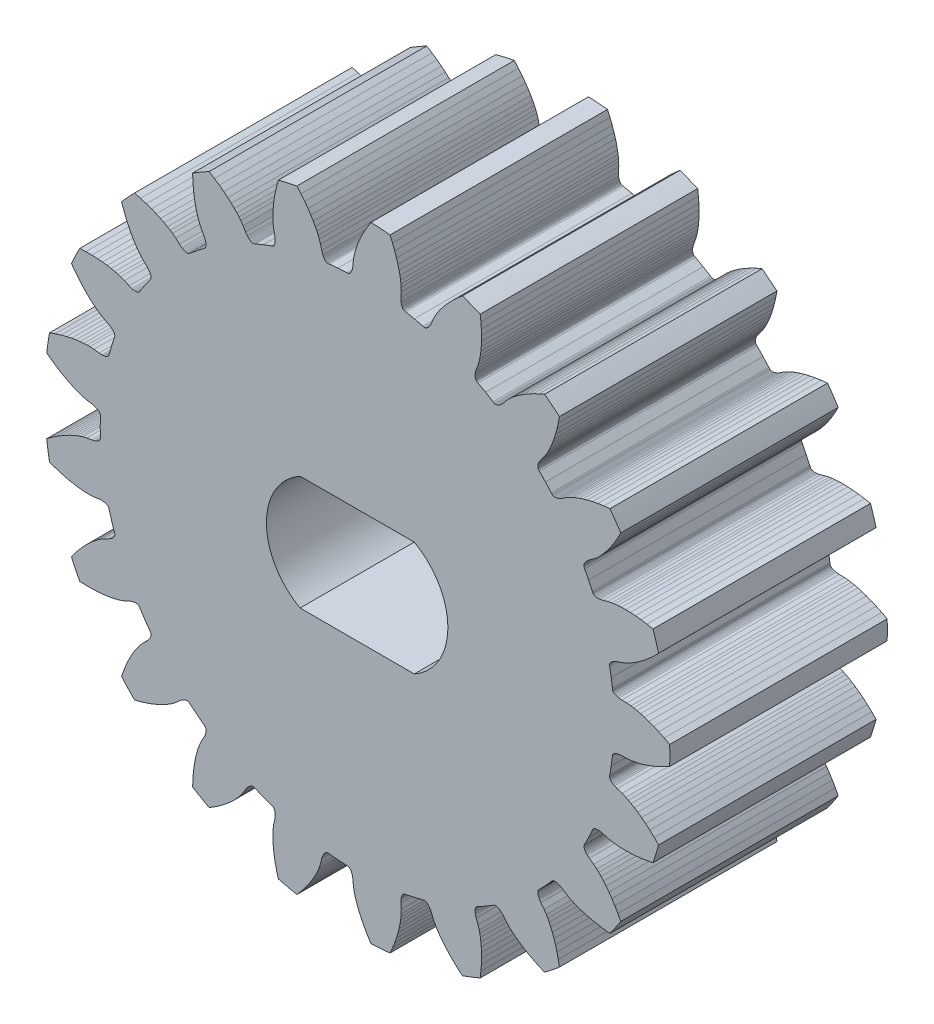
SolidWorks part; units mm, degrees
ref_plane "Front Plane" through (0, 0, 0) normal (0, 0, 1) x (1, 0, 0)
ref_plane "Top Plane" through (0, 0, 0) normal (0, 1, 0) x (1, 0, 0)
ref_plane "Right Plane" through (0, 0, 0) normal (1, 0, 0) x (0, 0, -1)
sketch "Model" plane through (0, 0, 0) normal (0, 0, 1) x (1, 0, 0)
  line L0 (10.9267, 2.8918) -> (10.7633, 2.7404)
  line L1 (10.7633, 2.7404) -> (10.6079, 2.6079)
  line L2 (10.6079, 2.6079) -> (10.4602, 2.4924)
  line L3 (10.4602, 2.4924) -> (10.3215, 2.3929)
  line L4 (10.3215, 2.3929) -> (10.1944, 2.3095)
  line L5 (10.1944, 2.3095) -> (10.0772, 2.2395)
  line L6 (10.0772, 2.2395) -> (9.9721, 2.1826)
  line L7 (9.9721, 2.1826) -> (9.8817, 2.1384)
  line L8 (9.8817, 2.1384) -> (9.7426, 2.0805)
  line L9 (9.7426, 2.0805) -> (9.5615, 2.023)
  line L10 (9.5615, 2.023) -> (9.4651, 1.9818)
  line L11 (9.4651, 1.9818) -> (9.4245, 1.9597)
  line L12 (9.4245, 1.9597) -> (9.3889, 1.9369)
  line L13 (9.3889, 1.9369) -> (9.3585, 1.9135)
  line L14 (9.3585, 1.9135) -> (9.3331, 1.8898)
  line L15 (9.3331, 1.8898) -> (9.3128, 1.866)
  line L16 (9.3128, 1.866) -> (9.2976, 1.8422)
  line L17 (9.2976, 1.8422) -> (9.2875, 1.8187)
  line L18 (9.2875, 1.8187) -> (9.2824, 1.7958)
  line L19 (9.2824, 1.7958) -> (9.2824, 1.7734)
  line L20 (9.2824, 1.7734) -> (9.291, 1.7262)
  line L21 (9.291, 1.7262) -> (9.3445, 1.4084)
  line L22 (9.3445, 1.4084) -> (9.3871, 1.0891)
  line L23 (9.3871, 1.0891) -> (9.3927, 1.0414)
  line L24 (9.3927, 1.0414) -> (9.3994, 1.0201)
  line L25 (9.3994, 1.0201) -> (9.411, 0.9996)
  line L26 (9.411, 0.9996) -> (9.4276, 0.9802)
  line L27 (9.4276, 0.9802) -> (9.4491, 0.9619)
  line L28 (9.4491, 0.9619) -> (9.4755, 0.9451)
  line L29 (9.4755, 0.9451) -> (9.5067, 0.93)
  line L30 (9.5067, 0.93) -> (9.5427, 0.9166)
  line L31 (9.5427, 0.9166) -> (9.5834, 0.9053)
  line L32 (9.5834, 0.9053) -> (9.6287, 0.8961)
  line L33 (9.6287, 0.8961) -> (9.733, 0.8852)
  line L34 (9.733, 0.8852) -> (9.923, 0.8836)
  line L35 (9.923, 0.8836) -> (10.073, 0.8693)
  line L36 (10.073, 0.8693) -> (10.1724, 0.8537)
  line L37 (10.1724, 0.8537) -> (10.2896, 0.8303)
  line L38 (10.2896, 0.8303) -> (10.4222, 0.7979)
  line L39 (10.4222, 0.7979) -> (10.5682, 0.7558)
  line L40 (10.5682, 0.7558) -> (10.7301, 0.7016)
  line L41 (10.7301, 0.7016) -> (10.9053, 0.6347)
  line L42 (10.9053, 0.6347) -> (11.0929, 0.5539)
  line L43 (11.0929, 0.5539) -> (11.2936, 0.4574)
  line L44 (11.2936, 0.4574) -> (11.4947, 0.3502)
  line L45 (11.4947, -0.3502) -> (11.2936, -0.4574)
  line L46 (11.2936, -0.4574) -> (11.0929, -0.5539)
  line L47 (11.0929, -0.5539) -> (10.9053, -0.6347)
  line L48 (10.9053, -0.6347) -> (10.7301, -0.7016)
  line L49 (10.7301, -0.7016) -> (10.5682, -0.7558)
  line L50 (10.5682, -0.7558) -> (10.4222, -0.7979)
  line L51 (10.4222, -0.7979) -> (10.2896, -0.8303)
  line L52 (10.2896, -0.8303) -> (10.1724, -0.8537)
  line L53 (10.1724, -0.8537) -> (10.073, -0.8693)
  line L54 (10.073, -0.8693) -> (9.923, -0.8836)
  line L55 (9.923, -0.8836) -> (9.733, -0.8852)
  line L56 (9.733, -0.8852) -> (9.6287, -0.8961)
  line L57 (9.6287, -0.8961) -> (9.5834, -0.9053)
  line L58 (9.5834, -0.9053) -> (9.5427, -0.9166)
  line L59 (9.5427, -0.9166) -> (9.5067, -0.93)
  line L60 (9.5067, -0.93) -> (9.4755, -0.9451)
  line L61 (9.4755, -0.9451) -> (9.4491, -0.9619)
  line L62 (9.4491, -0.9619) -> (9.4276, -0.9802)
  line L63 (9.4276, -0.9802) -> (9.411, -0.9996)
  line L64 (9.411, -0.9996) -> (9.3994, -1.0201)
  line L65 (9.3994, -1.0201) -> (9.3927, -1.0414)
  line L66 (9.3927, -1.0414) -> (9.3871, -1.0891)
  line L67 (9.3871, -1.0891) -> (9.3445, -1.4084)
  line L68 (9.3445, -1.4084) -> (9.291, -1.7262)
  line L69 (9.291, -1.7262) -> (9.2824, -1.7734)
  line L70 (9.2824, -1.7734) -> (9.2824, -1.7958)
  line L71 (9.2824, -1.7958) -> (9.2875, -1.8187)
  line L72 (9.2875, -1.8187) -> (9.2976, -1.8422)
  line L73 (9.2976, -1.8422) -> (9.3128, -1.866)
  line L74 (9.3128, -1.866) -> (9.3331, -1.8898)
  line L75 (9.3331, -1.8898) -> (9.3585, -1.9135)
  line L76 (9.3585, -1.9135) -> (9.3889, -1.9369)
  line L77 (9.3889, -1.9369) -> (9.4245, -1.9597)
  line L78 (9.4245, -1.9597) -> (9.4651, -1.9818)
  line L79 (9.4651, -1.9818) -> (9.5615, -2.023)
  line L80 (9.5615, -2.023) -> (9.7426, -2.0805)
  line L81 (9.7426, -2.0805) -> (9.8817, -2.1384)
  line L82 (9.8817, -2.1384) -> (9.9721, -2.1826)
  line L83 (9.9721, -2.1826) -> (10.0772, -2.2395)
  line L84 (10.0772, -2.2395) -> (10.1944, -2.3095)
  line L85 (10.1944, -2.3095) -> (10.3215, -2.3929)
  line L86 (10.3215, -2.3929) -> (10.4602, -2.4924)
  line L87 (10.4602, -2.4924) -> (10.6079, -2.6079)
  line L88 (10.6079, -2.6079) -> (10.7633, -2.7404)
  line L89 (10.7633, -2.7404) -> (10.9267, -2.8918)
  line L90 (10.9267, -2.8918) -> (11.0872, -3.0535)
  line L91 (10.8808, -3.7227) -> (10.657, -3.7659)
  line L92 (10.657, -3.7659) -> (10.4368, -3.799)
  line L93 (10.4368, -3.799) -> (10.2338, -3.8209)
  line L94 (10.2338, -3.8209) -> (10.0466, -3.8332)
  line L95 (10.0466, -3.8332) -> (9.8759, -3.8372)
  line L96 (9.8759, -3.8372) -> (9.724, -3.8345)
  line L97 (9.724, -3.8345) -> (9.5877, -3.8263)
  line L98 (9.5877, -3.8263) -> (9.4689, -3.8142)
  line L99 (9.4689, -3.8142) -> (9.3693, -3.7997)
  line L100 (9.3693, -3.7997) -> (9.2217, -3.7692)
  line L101 (9.2217, -3.7692) -> (9.0397, -3.7147)
  line L102 (9.0397, -3.7147) -> (8.9368, -3.6944)
  line L103 (8.9368, -3.6944) -> (8.8908, -3.6898)
  line L104 (8.8908, -3.6898) -> (8.8486, -3.6886)
  line L105 (8.8486, -3.6886) -> (8.8103, -3.6908)
  line L106 (8.8103, -3.6908) -> (8.7759, -3.6961)
  line L107 (8.7759, -3.6961) -> (8.7458, -3.7044)
  line L108 (8.7458, -3.7044) -> (8.7198, -3.7154)
  line L109 (8.7198, -3.7154) -> (8.6982, -3.7291)
  line L110 (8.6982, -3.7291) -> (8.6811, -3.7453)
  line L111 (8.6811, -3.7453) -> (8.6685, -3.7637)
  line L112 (8.6685, -3.7637) -> (8.649, -3.8076)
  line L113 (8.649, -3.8076) -> (8.5142, -4.1002)
  line L114 (8.5142, -4.1002) -> (8.3695, -4.3881)
  line L115 (8.3695, -4.3881) -> (8.3473, -4.4307)
  line L116 (8.3473, -4.4307) -> (8.3407, -4.452)
  line L117 (8.3407, -4.452) -> (8.3388, -4.4755)
  line L118 (8.3388, -4.4755) -> (8.3416, -4.5009)
  line L119 (8.3416, -4.5009) -> (8.3491, -4.5281)
  line L120 (8.3491, -4.5281) -> (8.3614, -4.5568)
  line L121 (8.3614, -4.5568) -> (8.3787, -4.587)
  line L122 (8.3787, -4.587) -> (8.4009, -4.6183)
  line L123 (8.4009, -4.6183) -> (8.4281, -4.6506)
  line L124 (8.4281, -4.6506) -> (8.4604, -4.6837)
  line L125 (8.4604, -4.6837) -> (8.5404, -4.7514)
  line L126 (8.5404, -4.7514) -> (8.6965, -4.8598)
  line L127 (8.6965, -4.8598) -> (8.8124, -4.9561)
  line L128 (8.8124, -4.9561) -> (8.8858, -5.025)
  line L129 (8.8858, -5.025) -> (8.9694, -5.1103)
  line L130 (8.9694, -5.1103) -> (9.0607, -5.2117)
  line L131 (9.0607, -5.2117) -> (9.1576, -5.3289)
  line L132 (9.1576, -5.3289) -> (9.2609, -5.4648)
  line L133 (9.2609, -5.4648) -> (9.3679, -5.6188)
  line L134 (9.3679, -5.6188) -> (9.4774, -5.7912)
  line L135 (9.4774, -5.7912) -> (9.5889, -5.984)
  line L136 (9.5889, -5.984) -> (9.6946, -6.1858)
  line L137 (9.3001, -6.7645) -> (9.0736, -6.7398)
  line L138 (9.0736, -6.7398) -> (8.8533, -6.7065)
  line L139 (8.8533, -6.7065) -> (8.6529, -6.6676)
  line L140 (8.6529, -6.6676) -> (8.4704, -6.6242)
  line L141 (8.4704, -6.6242) -> (8.3061, -6.5777)
  line L142 (8.3061, -6.5777) -> (8.1617, -6.5303)
  line L143 (8.1617, -6.5303) -> (8.0339, -6.4824)
  line L144 (8.0339, -6.4824) -> (7.9239, -6.4357)
  line L145 (7.9239, -6.4357) -> (7.833, -6.3926)
  line L146 (7.833, -6.3926) -> (7.701, -6.3199)
  line L147 (7.701, -6.3199) -> (7.5431, -6.2141)
  line L148 (7.5431, -6.2141) -> (7.4508, -6.1645)
  line L149 (7.4508, -6.1645) -> (7.4082, -6.1465)
  line L150 (7.4082, -6.1465) -> (7.3682, -6.1329)
  line L151 (7.3682, -6.1329) -> (7.331, -6.1237)
  line L152 (7.331, -6.1237) -> (7.2966, -6.1186)
  line L153 (7.2966, -6.1186) -> (7.2653, -6.1177)
  line L154 (7.2653, -6.1177) -> (7.2373, -6.1206)
  line L155 (7.2373, -6.1206) -> (7.2126, -6.1273)
  line L156 (7.2126, -6.1273) -> (7.1915, -6.1377)
  line L157 (7.1915, -6.1377) -> (7.174, -6.1515)
  line L158 (7.174, -6.1515) -> (7.1425, -6.1878)
  line L159 (7.1425, -6.1878) -> (6.9273, -6.4276)
  line L160 (6.9273, -6.4276) -> (6.7042, -6.6601)
  line L161 (6.7042, -6.6601) -> (6.6705, -6.6942)
  line L162 (6.6705, -6.6942) -> (6.6579, -6.7127)
  line L163 (6.6579, -6.7127) -> (6.6492, -6.7346)
  line L164 (6.6492, -6.7346) -> (6.6443, -6.7597)
  line L165 (6.6443, -6.7597) -> (6.6435, -6.7879)
  line L166 (6.6435, -6.7879) -> (6.6468, -6.819)
  line L167 (6.6468, -6.819) -> (6.6544, -6.8528)
  line L168 (6.6544, -6.8528) -> (6.6664, -6.8893)
  line L169 (6.6664, -6.8893) -> (6.6829, -6.9282)
  line L170 (6.6829, -6.9282) -> (6.704, -6.9693)
  line L171 (6.704, -6.9693) -> (6.7605, -7.0577)
  line L172 (6.7605, -7.0577) -> (6.8777, -7.2072)
  line L173 (6.8777, -7.2072) -> (6.9601, -7.3334)
  line L174 (6.9601, -7.3334) -> (7.0099, -7.4208)
  line L175 (7.0099, -7.4208) -> (7.0646, -7.527)
  line L176 (7.0646, -7.527) -> (7.122, -7.6509)
  line L177 (7.122, -7.6509) -> (7.1801, -7.7914)
  line L178 (7.1801, -7.7914) -> (7.2387, -7.9517)
  line L179 (7.2387, -7.9517) -> (7.2956, -8.1304)
  line L180 (7.2956, -8.1304) -> (7.3494, -8.3274)
  line L181 (7.3494, -8.3274) -> (7.399, -8.5445)
  line L182 (7.399, -8.5445) -> (7.4406, -8.7685)
  line L183 (6.893, -9.2052) -> (6.6839, -9.1149)
  line L184 (6.6839, -9.1149) -> (6.4832, -9.0181)
  line L185 (6.4832, -9.0181) -> (6.3032, -8.9218)
  line L186 (6.3032, -8.9218) -> (6.1416, -8.8266)
  line L187 (6.1416, -8.8266) -> (5.9983, -8.7338)
  line L188 (5.9983, -8.7338) -> (5.8743, -8.6459)
  line L189 (5.8743, -8.6459) -> (5.7663, -8.5624)
  line L190 (5.7663, -8.5624) -> (5.6749, -8.4854)
  line L191 (5.6749, -8.4854) -> (5.6008, -8.4174)
  line L192 (5.6008, -8.4174) -> (5.4961, -8.309)
  line L193 (5.4961, -8.309) -> (5.3764, -8.1614)
  line L194 (5.3764, -8.1614) -> (5.3028, -8.0868)
  line L195 (5.3028, -8.0868) -> (5.2674, -8.057)
  line L196 (5.2674, -8.057) -> (5.2332, -8.0323)
  line L197 (5.2332, -8.0323) -> (5.2003, -8.0125)
  line L198 (5.2003, -8.0125) -> (5.1689, -7.9975)
  line L199 (5.1689, -7.9975) -> (5.1394, -7.9874)
  line L200 (5.1394, -7.9874) -> (5.1117, -7.9819)
  line L201 (5.1117, -7.9819) -> (5.0861, -7.981)
  line L202 (5.0861, -7.981) -> (5.0629, -7.9847)
  line L203 (5.0629, -7.9847) -> (5.0421, -7.9928)
  line L204 (5.0421, -7.9928) -> (5.0013, -8.0181)
  line L205 (5.0013, -8.0181) -> (4.725, -8.1839)
  line L206 (4.725, -8.1839) -> (4.4433, -8.3403)
  line L207 (4.4433, -8.3403) -> (4.4009, -8.363)
  line L208 (4.4009, -8.363) -> (4.3835, -8.3769)
  line L209 (4.3835, -8.3769) -> (4.3687, -8.3952)
  line L210 (4.3687, -8.3952) -> (4.3567, -8.4178)
  line L211 (4.3567, -8.4178) -> (4.3476, -8.4445)
  line L212 (4.3476, -8.4445) -> (4.3416, -8.4752)
  line L213 (4.3416, -8.4752) -> (4.3389, -8.5098)
  line L214 (4.3389, -8.5098) -> (4.3396, -8.5482)
  line L215 (4.3396, -8.5482) -> (4.3439, -8.5902)
  line L216 (4.3439, -8.5902) -> (4.3519, -8.6358)
  line L217 (4.3519, -8.6358) -> (4.3798, -8.7368)
  line L218 (4.3798, -8.7368) -> (4.4478, -8.9142)
  line L219 (4.4478, -8.9142) -> (4.4893, -9.0591)
  line L220 (4.4893, -9.0591) -> (4.5111, -9.1574)
  line L221 (4.5111, -9.1574) -> (4.5321, -9.275)
  line L222 (4.5321, -9.275) -> (4.5504, -9.4102)
  line L223 (4.5504, -9.4102) -> (4.5645, -9.5616)
  line L224 (4.5645, -9.5616) -> (4.5732, -9.7321)
  line L225 (4.5732, -9.7321) -> (4.575, -9.9196)
  line L226 (4.575, -9.9196) -> (4.5683, -10.1237)
  line L227 (4.5683, -10.1237) -> (4.5518, -10.3458)
  line L228 (4.5518, -10.3458) -> (4.5254, -10.5721)
  line L229 (3.8735, -10.828) -> (3.7003, -10.68)
  line L230 (3.7003, -10.68) -> (3.537, -10.5284)
  line L231 (3.537, -10.5284) -> (3.3934, -10.3834)
  line L232 (3.3934, -10.3834) -> (3.2671, -10.2447)
  line L233 (3.2671, -10.2447) -> (3.1575, -10.1138)
  line L234 (3.1575, -10.1138) -> (3.0649, -9.9933)
  line L235 (3.0649, -9.9933) -> (2.9863, -9.8817)
  line L236 (2.9863, -9.8817) -> (2.9217, -9.7812)
  line L237 (2.9217, -9.7812) -> (2.8709, -9.6943)
  line L238 (2.8709, -9.6943) -> (2.8028, -9.5598)
  line L239 (2.8028, -9.5598) -> (2.7319, -9.3836)
  line L240 (2.7319, -9.3836) -> (2.6836, -9.2905)
  line L241 (2.6836, -9.2905) -> (2.6585, -9.2517)
  line L242 (2.6585, -9.2517) -> (2.6331, -9.2179)
  line L243 (2.6331, -9.2179) -> (2.6075, -9.1893)
  line L244 (2.6075, -9.1893) -> (2.582, -9.1658)
  line L245 (2.582, -9.1658) -> (2.5567, -9.1474)
  line L246 (2.5567, -9.1474) -> (2.5319, -9.134)
  line L247 (2.5319, -9.134) -> (2.5077, -9.1256)
  line L248 (2.5077, -9.1256) -> (2.4844, -9.1223)
  line L249 (2.4844, -9.1223) -> (2.4622, -9.1239)
  line L250 (2.4622, -9.1239) -> (2.4157, -9.1361)
  line L251 (2.4157, -9.1361) -> (2.1028, -9.2131)
  line L252 (2.1028, -9.2131) -> (1.7875, -9.2794)
  line L253 (1.7875, -9.2794) -> (1.7404, -9.2886)
  line L254 (1.7404, -9.2886) -> (1.7196, -9.2968)
  line L255 (1.7196, -9.2968) -> (1.7001, -9.31)
  line L256 (1.7001, -9.31) -> (1.6819, -9.328)
  line L257 (1.6819, -9.328) -> (1.6654, -9.3508)
  line L258 (1.6654, -9.3508) -> (1.6506, -9.3784)
  line L259 (1.6506, -9.3784) -> (1.6378, -9.4106)
  line L260 (1.6378, -9.4106) -> (1.6272, -9.4475)
  line L261 (1.6272, -9.4475) -> (1.6189, -9.489)
  line L262 (1.6189, -9.489) -> (1.6132, -9.5348)
  line L263 (1.6132, -9.5348) -> (1.61, -9.6396)
  line L264 (1.61, -9.6396) -> (1.6227, -9.8292)
  line L265 (1.6227, -9.8292) -> (1.6196, -9.9799)
  line L266 (1.6196, -9.9799) -> (1.6115, -10.0802)
  line L267 (1.6115, -10.0802) -> (1.5969, -10.1988)
  line L268 (1.5969, -10.1988) -> (1.5746, -10.3334)
  line L269 (1.5746, -10.3334) -> (1.5434, -10.4822)
  line L270 (1.5434, -10.4822) -> (1.5015, -10.6477)
  line L271 (1.5015, -10.6477) -> (1.4479, -10.8274)
  line L272 (1.4479, -10.8274) -> (1.3814, -11.0205)
  line L273 (1.3814, -11.0205) -> (1.3001, -11.2278)
  line L274 (1.3001, -11.2278) -> (1.2082, -11.4363)
  line L275 (0.5098, -11.4887) -> (0.3879, -11.2962)
  line L276 (0.3879, -11.2962) -> (0.2766, -11.1032)
  line L277 (0.2766, -11.1032) -> (0.1821, -10.9223)
  line L278 (0.1821, -10.9223) -> (0.1022, -10.7526)
  line L279 (0.1022, -10.7526) -> (0.0361, -10.5952)
  line L280 (0.0361, -10.5952) -> (-0.0169, -10.4527)
  line L281 (-0.0169, -10.4527) -> (-0.059, -10.3229)
  line L282 (-0.059, -10.3229) -> (-0.0911, -10.2078)
  line L283 (-0.0911, -10.2078) -> (-0.1141, -10.1098)
  line L284 (-0.1141, -10.1098) -> (-0.1396, -9.9613)
  line L285 (-0.1396, -9.9613) -> (-0.1553, -9.7719)
  line L286 (-0.1553, -9.7719) -> (-0.174, -9.6688)
  line L287 (-0.174, -9.6688) -> (-0.1866, -9.6243)
  line L288 (-0.1866, -9.6243) -> (-0.2009, -9.5845)
  line L289 (-0.2009, -9.5845) -> (-0.2169, -9.5496)
  line L290 (-0.2169, -9.5496) -> (-0.2344, -9.5196)
  line L291 (-0.2344, -9.5196) -> (-0.2531, -9.4946)
  line L292 (-0.2531, -9.4946) -> (-0.2729, -9.4745)
  line L293 (-0.2729, -9.4745) -> (-0.2935, -9.4594)
  line L294 (-0.2935, -9.4594) -> (-0.3148, -9.4493)
  line L295 (-0.3148, -9.4493) -> (-0.3366, -9.4443)
  line L296 (-0.3366, -9.4443) -> (-0.3845, -9.4422)
  line L297 (-0.3845, -9.4422) -> (-0.7062, -9.4236)
  line L298 (-0.7062, -9.4236) -> (-1.027, -9.3941)
  line L299 (-1.027, -9.3941) -> (-1.0748, -9.389)
  line L300 (-1.0748, -9.389) -> (-1.0971, -9.3907)
  line L301 (-1.0971, -9.3907) -> (-1.1196, -9.3975)
  line L302 (-1.1196, -9.3975) -> (-1.1423, -9.4093)
  line L303 (-1.1423, -9.4093) -> (-1.1648, -9.4262)
  line L304 (-1.1648, -9.4262) -> (-1.1871, -9.4482)
  line L305 (-1.1871, -9.4482) -> (-1.2088, -9.4753)
  line L306 (-1.2088, -9.4753) -> (-1.2298, -9.5074)
  line L307 (-1.2298, -9.5074) -> (-1.25, -9.5446)
  line L308 (-1.25, -9.5446) -> (-1.269, -9.5867)
  line L309 (-1.269, -9.5867) -> (-1.3028, -9.6859)
  line L310 (-1.3028, -9.6859) -> (-1.3466, -9.8708)
  line L311 (-1.3466, -9.8708) -> (-1.394, -10.0139)
  line L312 (-1.394, -10.0139) -> (-1.4313, -10.1074)
  line L313 (-1.4313, -10.1074) -> (-1.4802, -10.2164)
  line L314 (-1.4802, -10.2164) -> (-1.5412, -10.3384)
  line L315 (-1.5412, -10.3384) -> (-1.6148, -10.4714)
  line L316 (-1.6148, -10.4714) -> (-1.7037, -10.6172)
  line L317 (-1.7037, -10.6172) -> (-1.8079, -10.7731)
  line L318 (-1.8079, -10.7731) -> (-1.9284, -10.938)
  line L319 (-1.9284, -10.938) -> (-2.0672, -11.1122)
  line L320 (-2.0672, -11.1122) -> (-2.2164, -11.2844)
  line L321 (-2.8992, -11.1285) -> (-2.959, -10.9087)
  line L322 (-2.959, -10.9087) -> (-3.0084, -10.6915)
  line L323 (-3.0084, -10.6915) -> (-3.0454, -10.4907)
  line L324 (-3.0454, -10.4907) -> (-3.0717, -10.305)
  line L325 (-3.0717, -10.305) -> (-3.0885, -10.1351)
  line L326 (-3.0885, -10.1351) -> (-3.0971, -9.9833)
  line L327 (-3.0971, -9.9833) -> (-3.0991, -9.8468)
  line L328 (-3.0991, -9.8468) -> (-3.0959, -9.7274)
  line L329 (-3.0959, -9.7274) -> (-3.089, -9.627)
  line L330 (-3.089, -9.627) -> (-3.0695, -9.4776)
  line L331 (-3.0695, -9.4776) -> (-3.0288, -9.292)
  line L332 (-3.0288, -9.292) -> (-3.0162, -9.1879)
  line L333 (-3.0162, -9.1879) -> (-3.0151, -9.1417)
  line L334 (-3.0151, -9.1417) -> (-3.0171, -9.0995)
  line L335 (-3.0171, -9.0995) -> (-3.0221, -9.0614)
  line L336 (-3.0221, -9.0614) -> (-3.0299, -9.0276)
  line L337 (-3.0299, -9.0276) -> (-3.0404, -8.9981)
  line L338 (-3.0404, -8.9981) -> (-3.0534, -8.9731)
  line L339 (-3.0534, -8.9731) -> (-3.0687, -8.9526)
  line L340 (-3.0687, -8.9526) -> (-3.0861, -8.9367)
  line L341 (-3.0861, -8.9367) -> (-3.1054, -8.9255)
  line L342 (-3.1054, -8.9255) -> (-3.1506, -8.9094)
  line L343 (-3.1506, -8.9094) -> (-3.4525, -8.7968)
  line L344 (-3.4525, -8.7968) -> (-3.7504, -8.674)
  line L345 (-3.7504, -8.674) -> (-3.7945, -8.655)
  line L346 (-3.7945, -8.655) -> (-3.8163, -8.6501)
  line L347 (-3.8163, -8.6501) -> (-3.8398, -8.65)
  line L348 (-3.8398, -8.65) -> (-3.8649, -8.6546)
  line L349 (-3.8649, -8.6546) -> (-3.8915, -8.6641)
  line L350 (-3.8915, -8.6641) -> (-3.9192, -8.6786)
  line L351 (-3.9192, -8.6786) -> (-3.948, -8.698)
  line L352 (-3.948, -8.698) -> (-3.9776, -8.7225)
  line L353 (-3.9776, -8.7225) -> (-4.0077, -8.7521)
  line L354 (-4.0077, -8.7521) -> (-4.0383, -8.7868)
  line L355 (-4.0383, -8.7868) -> (-4.0999, -8.8716)
  line L356 (-4.0999, -8.8716) -> (-4.1963, -9.0353)
  line L357 (-4.1963, -9.0353) -> (-4.2837, -9.1581)
  line L358 (-4.2837, -9.1581) -> (-4.3469, -9.2364)
  line L359 (-4.3469, -9.2364) -> (-4.4257, -9.3262)
  line L360 (-4.4257, -9.3262) -> (-4.5201, -9.4249)
  line L361 (-4.5201, -9.4249) -> (-4.6296, -9.5302)
  line L362 (-4.6296, -9.5302) -> (-4.7575, -9.6434)
  line L363 (-4.7575, -9.6434) -> (-4.903, -9.7616)
  line L364 (-4.903, -9.7616) -> (-5.0667, -9.8837)
  line L365 (-5.0667, -9.8837) -> (-5.2507, -10.0092)
  line L366 (-5.2507, -10.0092) -> (-5.4441, -10.1297)
  line L367 (-6.0506, -9.7796) -> (-6.0429, -9.5519)
  line L368 (-6.0429, -9.5519) -> (-6.0262, -9.3297)
  line L369 (-6.0262, -9.3297) -> (-6.0023, -9.127)
  line L370 (-6.0023, -9.127) -> (-5.9727, -8.9418)
  line L371 (-5.9727, -8.9418) -> (-5.9386, -8.7745)
  line L372 (-5.9386, -8.7745) -> (-5.9021, -8.6269)
  line L373 (-5.9021, -8.6269) -> (-5.8639, -8.4959)
  line L374 (-5.8639, -8.4959) -> (-5.8256, -8.3827)
  line L375 (-5.8256, -8.3827) -> (-5.7893, -8.2888)
  line L376 (-5.7893, -8.2888) -> (-5.7267, -8.1517)
  line L377 (-5.7267, -8.1517) -> (-5.6331, -7.9864)
  line L378 (-5.6331, -7.9864) -> (-5.5904, -7.8907)
  line L379 (-5.5904, -7.8907) -> (-5.5757, -7.8468)
  line L380 (-5.5757, -7.8468) -> (-5.5652, -7.8059)
  line L381 (-5.5652, -7.8059) -> (-5.5587, -7.7681)
  line L382 (-5.5587, -7.7681) -> (-5.5563, -7.7334)
  line L383 (-5.5563, -7.7334) -> (-5.5576, -7.7022)
  line L384 (-5.5576, -7.7022) -> (-5.5626, -7.6744)
  line L385 (-5.5626, -7.6744) -> (-5.5712, -7.6504)
  line L386 (-5.5712, -7.6504) -> (-5.5831, -7.63)
  line L387 (-5.5831, -7.63) -> (-5.5982, -7.6136)
  line L388 (-5.5982, -7.6136) -> (-5.6367, -7.5849)
  line L389 (-5.6367, -7.5849) -> (-5.892, -7.3883)
  line L390 (-5.892, -7.3883) -> (-6.1404, -7.1832)
  line L391 (-6.1404, -7.1832) -> (-6.177, -7.1521)
  line L392 (-6.177, -7.1521) -> (-6.1964, -7.141)
  line L393 (-6.1964, -7.141) -> (-6.2188, -7.1339)
  line L394 (-6.2188, -7.1339) -> (-6.2442, -7.1309)
  line L395 (-6.2442, -7.1309) -> (-6.2724, -7.1322)
  line L396 (-6.2724, -7.1322) -> (-6.3032, -7.1378)
  line L397 (-6.3032, -7.1378) -> (-6.3364, -7.1479)
  line L398 (-6.3364, -7.1479) -> (-6.3719, -7.1626)
  line L399 (-6.3719, -7.1626) -> (-6.4094, -7.182)
  line L400 (-6.4094, -7.182) -> (-6.4489, -7.2061)
  line L401 (-6.4489, -7.2061) -> (-6.5327, -7.269)
  line L402 (-6.5327, -7.269) -> (-6.6731, -7.3971)
  line L403 (-6.6731, -7.3971) -> (-6.7928, -7.4886)
  line L404 (-6.7928, -7.4886) -> (-6.8762, -7.5448)
  line L405 (-6.8762, -7.5448) -> (-6.978, -7.6074)
  line L406 (-6.978, -7.6074) -> (-7.0973, -7.6738)
  line L407 (-7.0973, -7.6738) -> (-7.233, -7.7422)
  line L408 (-7.233, -7.7422) -> (-7.3886, -7.8126)
  line L409 (-7.3886, -7.8126) -> (-7.5625, -7.8828)
  line L410 (-7.5625, -7.8828) -> (-7.7549, -7.9511)
  line L411 (-7.7549, -7.9511) -> (-7.9677, -8.0169)
  line L412 (-7.9677, -8.0169) -> (-8.188, -8.075)
  line L413 (-8.6644, -7.5617) -> (-8.5899, -7.3463)
  line L414 (-8.5899, -7.3463) -> (-8.5084, -7.139)
  line L415 (-8.5084, -7.139) -> (-8.4259, -6.9523)
  line L416 (-8.4259, -6.9523) -> (-8.3429, -6.7841)
  line L417 (-8.3429, -6.7841) -> (-8.2611, -6.6342)
  line L418 (-8.2611, -6.6342) -> (-8.1827, -6.504)
  line L419 (-8.1827, -6.504) -> (-8.1076, -6.39)
  line L420 (-8.1076, -6.39) -> (-8.0376, -6.2932)
  line L421 (-8.0376, -6.2932) -> (-7.9753, -6.2141)
  line L422 (-7.9753, -6.2141) -> (-7.875, -6.1016)
  line L423 (-7.875, -6.1016) -> (-7.7368, -5.9712)
  line L424 (-7.7368, -5.9712) -> (-7.6679, -5.8923)
  line L425 (-7.6679, -5.8923) -> (-7.6409, -5.8548)
  line L426 (-7.6409, -5.8548) -> (-7.6188, -5.8188)
  line L427 (-7.6188, -5.8188) -> (-7.6015, -5.7845)
  line L428 (-7.6015, -5.7845) -> (-7.5889, -5.7521)
  line L429 (-7.5889, -5.7521) -> (-7.581, -5.7219)
  line L430 (-7.581, -5.7219) -> (-7.5776, -5.6939)
  line L431 (-7.5776, -5.6939) -> (-7.5786, -5.6683)
  line L432 (-7.5786, -5.6683) -> (-7.584, -5.6454)
  line L433 (-7.584, -5.6454) -> (-7.5937, -5.6253)
  line L434 (-7.5937, -5.6253) -> (-7.622, -5.5865)
  line L435 (-7.622, -5.5865) -> (-7.808, -5.3234)
  line L436 (-7.808, -5.3234) -> (-7.9849, -5.0541)
  line L437 (-7.9849, -5.0541) -> (-8.0107, -5.0136)
  line L438 (-8.0107, -5.0136) -> (-8.0259, -4.9973)
  line L439 (-8.0259, -4.9973) -> (-8.0453, -4.9839)
  line L440 (-8.0453, -4.9839) -> (-8.0687, -4.9736)
  line L441 (-8.0687, -4.9736) -> (-8.096, -4.9665)
  line L442 (-8.096, -4.9665) -> (-8.127, -4.9628)
  line L443 (-8.127, -4.9628) -> (-8.1618, -4.9627)
  line L444 (-8.1618, -4.9627) -> (-8.2, -4.9663)
  line L445 (-8.2, -4.9663) -> (-8.2416, -4.9737)
  line L446 (-8.2416, -4.9737) -> (-8.2864, -4.9851)
  line L447 (-8.2864, -4.9851) -> (-8.3851, -5.0205)
  line L448 (-8.3851, -5.0205) -> (-8.5569, -5.1015)
  line L449 (-8.5569, -5.1015) -> (-8.6983, -5.1537)
  line L450 (-8.6983, -5.1537) -> (-8.7946, -5.1828)
  line L451 (-8.7946, -5.1828) -> (-8.9103, -5.2126)
  line L452 (-8.9103, -5.2126) -> (-9.0439, -5.2409)
  line L453 (-9.0439, -5.2409) -> (-9.1937, -5.2663)
  line L454 (-9.1937, -5.2663) -> (-9.3631, -5.2877)
  line L455 (-9.3631, -5.2877) -> (-9.55, -5.3035)
  line L456 (-9.55, -5.3035) -> (-9.754, -5.3121)
  line L457 (-9.754, -5.3121) -> (-9.9767, -5.3122)
  line L458 (-9.9767, -5.3122) -> (-10.2044, -5.3028)
  line L459 (-10.5083, -4.6718) -> (-10.3736, -4.488)
  line L460 (-10.3736, -4.488) -> (-10.2347, -4.3139)
  line L461 (-10.2347, -4.3139) -> (-10.1007, -4.1598)
  line L462 (-10.1007, -4.1598) -> (-9.9719, -4.0235)
  line L463 (-9.9719, -4.0235) -> (-9.8496, -3.9045)
  line L464 (-9.8496, -3.9045) -> (-9.7363, -3.8031)
  line L465 (-9.7363, -3.8031) -> (-9.6309, -3.7164)
  line L466 (-9.6309, -3.7164) -> (-9.5355, -3.6445)
  line L467 (-9.5355, -3.6445) -> (-9.4526, -3.5873)
  line L468 (-9.4526, -3.5873) -> (-9.3237, -3.5093)
  line L469 (-9.3237, -3.5093) -> (-9.1532, -3.4255)
  line L470 (-9.1532, -3.4255) -> (-9.064, -3.3704)
  line L471 (-9.064, -3.3704) -> (-9.0271, -3.3425)
  line L472 (-9.0271, -3.3425) -> (-8.9954, -3.3146)
  line L473 (-8.9954, -3.3146) -> (-8.9688, -3.2869)
  line L474 (-8.9688, -3.2869) -> (-8.9472, -3.2597)
  line L475 (-8.9472, -3.2597) -> (-8.9307, -3.2331)
  line L476 (-8.9307, -3.2331) -> (-8.9192, -3.2074)
  line L477 (-8.9192, -3.2074) -> (-8.9127, -3.1827)
  line L478 (-8.9127, -3.1827) -> (-8.9111, -3.1592)
  line L479 (-8.9111, -3.1592) -> (-8.9144, -3.1371)
  line L480 (-8.9144, -3.1371) -> (-8.93, -3.0917)
  line L481 (-8.93, -3.0917) -> (-9.0302, -2.7854)
  line L482 (-9.0302, -2.7854) -> (-9.1199, -2.476)
  line L483 (-9.1199, -2.476) -> (-9.1326, -2.4297)
  line L484 (-9.1326, -2.4297) -> (-9.1423, -2.4096)
  line L485 (-9.1423, -2.4096) -> (-9.1569, -2.3911)
  line L486 (-9.1569, -2.3911) -> (-9.1762, -2.3743)
  line L487 (-9.1762, -2.3743) -> (-9.2002, -2.3595)
  line L488 (-9.2002, -2.3595) -> (-9.2288, -2.3468)
  line L489 (-9.2288, -2.3468) -> (-9.2619, -2.3365)
  line L490 (-9.2619, -2.3365) -> (-9.2995, -2.3286)
  line L491 (-9.2995, -2.3286) -> (-9.3414, -2.3235)
  line L492 (-9.3414, -2.3235) -> (-9.3876, -2.3212)
  line L493 (-9.3876, -2.3212) -> (-9.4923, -2.3259)
  line L494 (-9.4923, -2.3259) -> (-9.6804, -2.3527)
  line L495 (-9.6804, -2.3527) -> (-9.8309, -2.3609)
  line L496 (-9.8309, -2.3609) -> (-9.9316, -2.3603)
  line L497 (-9.9316, -2.3603) -> (-10.0509, -2.3546)
  line L498 (-10.0509, -2.3546) -> (-10.1869, -2.3424)
  line L499 (-10.1869, -2.3424) -> (-10.3375, -2.3224)
  line L500 (-10.3375, -2.3224) -> (-10.5057, -2.293)
  line L501 (-10.5057, -2.293) -> (-10.6889, -2.2529)
  line L502 (-10.6889, -2.2529) -> (-10.8864, -2.2011)
  line L503 (-10.8864, -2.2011) -> (-11.0993, -2.1355)
  line L504 (-11.0993, -2.1355) -> (-11.3141, -2.0595)
  line L505 (-11.4185, -1.3669) -> (-11.2356, -1.231)
  line L506 (-11.2356, -1.231) -> (-11.0515, -1.1056)
  line L507 (-11.0515, -1.1056) -> (-10.8781, -0.9978)
  line L508 (-10.8781, -0.9978) -> (-10.7149, -0.9055)
  line L509 (-10.7149, -0.9055) -> (-10.5628, -0.8278)
  line L510 (-10.5628, -0.8278) -> (-10.4247, -0.7643)
  line L511 (-10.4247, -0.7643) -> (-10.2984, -0.7125)
  line L512 (-10.2984, -0.7125) -> (-10.1861, -0.6719)
  line L513 (-10.1861, -0.6719) -> (-10.0901, -0.6417)
  line L514 (-10.0901, -0.6417) -> (-9.9438, -0.6052)
  line L515 (-9.9438, -0.6052) -> (-9.7562, -0.5753)
  line L516 (-9.7562, -0.5753) -> (-9.6547, -0.549)
  line L517 (-9.6547, -0.549) -> (-9.6113, -0.5332)
  line L518 (-9.6113, -0.5332) -> (-9.5727, -0.5159)
  line L519 (-9.5727, -0.5159) -> (-9.5391, -0.4973)
  line L520 (-9.5391, -0.4973) -> (-9.5105, -0.4777)
  line L521 (-9.5105, -0.4777) -> (-9.4869, -0.4571)
  line L522 (-9.4869, -0.4571) -> (-9.4684, -0.4359)
  line L523 (-9.4684, -0.4359) -> (-9.4549, -0.4142)
  line L524 (-9.4549, -0.4142) -> (-9.4464, -0.3922)
  line L525 (-9.4464, -0.3922) -> (-9.443, -0.3702)
  line L526 (-9.443, -0.3702) -> (-9.4445, -0.3221)
  line L527 (-9.4445, -0.3221) -> (-9.45, 0)
  line L528 (-9.45, 0) -> (-9.4445, 0.3221)
  line L529 (-9.4445, 0.3221) -> (-9.443, 0.3702)
  line L530 (-9.443, 0.3702) -> (-9.4464, 0.3922)
  line L531 (-9.4464, 0.3922) -> (-9.4549, 0.4142)
  line L532 (-9.4549, 0.4142) -> (-9.4684, 0.4359)
  line L533 (-9.4684, 0.4359) -> (-9.4869, 0.4571)
  line L534 (-9.4869, 0.4571) -> (-9.5105, 0.4777)
  line L535 (-9.5105, 0.4777) -> (-9.5391, 0.4973)
  line L536 (-9.5391, 0.4973) -> (-9.5727, 0.5159)
  line L537 (-9.5727, 0.5159) -> (-9.6113, 0.5332)
  line L538 (-9.6113, 0.5332) -> (-9.6547, 0.549)
  line L539 (-9.6547, 0.549) -> (-9.7562, 0.5753)
  line L540 (-9.7562, 0.5753) -> (-9.9438, 0.6052)
  line L541 (-9.9438, 0.6052) -> (-10.0901, 0.6417)
  line L542 (-10.0901, 0.6417) -> (-10.1861, 0.6719)
  line L543 (-10.1861, 0.6719) -> (-10.2984, 0.7125)
  line L544 (-10.2984, 0.7125) -> (-10.4247, 0.7643)
  line L545 (-10.4247, 0.7643) -> (-10.5628, 0.8278)
  line L546 (-10.5628, 0.8278) -> (-10.7149, 0.9055)
  line L547 (-10.7149, 0.9055) -> (-10.8781, 0.9978)
  line L548 (-10.8781, 0.9978) -> (-11.0515, 1.1056)
  line L549 (-11.0515, 1.1056) -> (-11.2356, 1.231)
  line L550 (-11.2356, 1.231) -> (-11.4185, 1.3669)
  line L551 (-11.3141, 2.0595) -> (-11.0993, 2.1355)
  line L552 (-11.0993, 2.1355) -> (-10.8864, 2.2011)
  line L553 (-10.8864, 2.2011) -> (-10.6889, 2.2529)
  line L554 (-10.6889, 2.2529) -> (-10.5057, 2.293)
  line L555 (-10.5057, 2.293) -> (-10.3375, 2.3224)
  line L556 (-10.3375, 2.3224) -> (-10.1869, 2.3424)
  line L557 (-10.1869, 2.3424) -> (-10.0509, 2.3546)
  line L558 (-10.0509, 2.3546) -> (-9.9316, 2.3603)
  line L559 (-9.9316, 2.3603) -> (-9.8309, 2.3609)
  line L560 (-9.8309, 2.3609) -> (-9.6804, 2.3527)
  line L561 (-9.6804, 2.3527) -> (-9.4923, 2.3259)
  line L562 (-9.4923, 2.3259) -> (-9.3876, 2.3212)
  line L563 (-9.3876, 2.3212) -> (-9.3414, 2.3235)
  line L564 (-9.3414, 2.3235) -> (-9.2995, 2.3286)
  line L565 (-9.2995, 2.3286) -> (-9.2619, 2.3365)
  line L566 (-9.2619, 2.3365) -> (-9.2288, 2.3468)
  line L567 (-9.2288, 2.3468) -> (-9.2002, 2.3595)
  line L568 (-9.2002, 2.3595) -> (-9.1762, 2.3743)
  line L569 (-9.1762, 2.3743) -> (-9.1569, 2.3911)
  line L570 (-9.1569, 2.3911) -> (-9.1423, 2.4096)
  line L571 (-9.1423, 2.4096) -> (-9.1326, 2.4297)
  line L572 (-9.1326, 2.4297) -> (-9.1199, 2.476)
  line L573 (-9.1199, 2.476) -> (-9.0302, 2.7854)
  line L574 (-9.0302, 2.7854) -> (-8.93, 3.0917)
  line L575 (-8.93, 3.0917) -> (-8.9144, 3.1371)
  line L576 (-8.9144, 3.1371) -> (-8.9111, 3.1592)
  line L577 (-8.9111, 3.1592) -> (-8.9127, 3.1827)
  line L578 (-8.9127, 3.1827) -> (-8.9192, 3.2074)
  line L579 (-8.9192, 3.2074) -> (-8.9307, 3.2331)
  line L580 (-8.9307, 3.2331) -> (-8.9472, 3.2597)
  line L581 (-8.9472, 3.2597) -> (-8.9688, 3.2869)
  line L582 (-8.9688, 3.2869) -> (-8.9954, 3.3146)
  line L583 (-8.9954, 3.3146) -> (-9.0271, 3.3425)
  line L584 (-9.0271, 3.3425) -> (-9.064, 3.3704)
  line L585 (-9.064, 3.3704) -> (-9.1532, 3.4255)
  line L586 (-9.1532, 3.4255) -> (-9.3237, 3.5093)
  line L587 (-9.3237, 3.5093) -> (-9.4526, 3.5873)
  line L588 (-9.4526, 3.5873) -> (-9.5355, 3.6445)
  line L589 (-9.5355, 3.6445) -> (-9.6309, 3.7164)
  line L590 (-9.6309, 3.7164) -> (-9.7363, 3.8031)
  line L591 (-9.7363, 3.8031) -> (-9.8496, 3.9045)
  line L592 (-9.8496, 3.9045) -> (-9.9719, 4.0235)
  line L593 (-9.9719, 4.0235) -> (-10.1007, 4.1598)
  line L594 (-10.1007, 4.1598) -> (-10.2347, 4.3139)
  line L595 (-10.2347, 4.3139) -> (-10.3736, 4.488)
  line L596 (-10.3736, 4.488) -> (-10.5083, 4.6718)
  line L597 (-10.2044, 5.3028) -> (-9.9767, 5.3122)
  line L598 (-9.9767, 5.3122) -> (-9.754, 5.3121)
  line L599 (-9.754, 5.3121) -> (-9.55, 5.3035)
  line L600 (-9.55, 5.3035) -> (-9.3631, 5.2877)
  line L601 (-9.3631, 5.2877) -> (-9.1937, 5.2663)
  line L602 (-9.1937, 5.2663) -> (-9.0439, 5.2409)
  line L603 (-9.0439, 5.2409) -> (-8.9103, 5.2126)
  line L604 (-8.9103, 5.2126) -> (-8.7946, 5.1828)
  line L605 (-8.7946, 5.1828) -> (-8.6983, 5.1537)
  line L606 (-8.6983, 5.1537) -> (-8.5569, 5.1015)
  line L607 (-8.5569, 5.1015) -> (-8.3851, 5.0205)
  line L608 (-8.3851, 5.0205) -> (-8.2864, 4.9851)
  line L609 (-8.2864, 4.9851) -> (-8.2416, 4.9737)
  line L610 (-8.2416, 4.9737) -> (-8.2, 4.9663)
  line L611 (-8.2, 4.9663) -> (-8.1618, 4.9627)
  line L612 (-8.1618, 4.9627) -> (-8.127, 4.9628)
  line L613 (-8.127, 4.9628) -> (-8.096, 4.9665)
  line L614 (-8.096, 4.9665) -> (-8.0687, 4.9736)
  line L615 (-8.0687, 4.9736) -> (-8.0453, 4.9839)
  line L616 (-8.0453, 4.9839) -> (-8.0259, 4.9973)
  line L617 (-8.0259, 4.9973) -> (-8.0107, 5.0136)
  line L618 (-8.0107, 5.0136) -> (-7.9849, 5.0541)
  line L619 (-7.9849, 5.0541) -> (-7.808, 5.3234)
  line L620 (-7.808, 5.3234) -> (-7.622, 5.5865)
  line L621 (-7.622, 5.5865) -> (-7.5937, 5.6253)
  line L622 (-7.5937, 5.6253) -> (-7.584, 5.6454)
  line L623 (-7.584, 5.6454) -> (-7.5786, 5.6683)
  line L624 (-7.5786, 5.6683) -> (-7.5776, 5.6939)
  line L625 (-7.5776, 5.6939) -> (-7.581, 5.7219)
  line L626 (-7.581, 5.7219) -> (-7.5889, 5.7521)
  line L627 (-7.5889, 5.7521) -> (-7.6015, 5.7845)
  line L628 (-7.6015, 5.7845) -> (-7.6188, 5.8188)
  line L629 (-7.6188, 5.8188) -> (-7.6409, 5.8548)
  line L630 (-7.6409, 5.8548) -> (-7.6679, 5.8923)
  line L631 (-7.6679, 5.8923) -> (-7.7368, 5.9712)
  line L632 (-7.7368, 5.9712) -> (-7.875, 6.1016)
  line L633 (-7.875, 6.1016) -> (-7.9753, 6.2141)
  line L634 (-7.9753, 6.2141) -> (-8.0376, 6.2932)
  line L635 (-8.0376, 6.2932) -> (-8.1076, 6.39)
  line L636 (-8.1076, 6.39) -> (-8.1827, 6.504)
  line L637 (-8.1827, 6.504) -> (-8.2611, 6.6342)
  line L638 (-8.2611, 6.6342) -> (-8.3429, 6.7841)
  line L639 (-8.3429, 6.7841) -> (-8.4259, 6.9523)
  line L640 (-8.4259, 6.9523) -> (-8.5084, 7.139)
  line L641 (-8.5084, 7.139) -> (-8.5899, 7.3463)
  line L642 (-8.5899, 7.3463) -> (-8.6644, 7.5617)
  line L643 (-8.188, 8.075) -> (-7.9677, 8.0169)
  line L644 (-7.9677, 8.0169) -> (-7.7549, 7.9511)
  line L645 (-7.7549, 7.9511) -> (-7.5625, 7.8828)
  line L646 (-7.5625, 7.8828) -> (-7.3886, 7.8126)
  line L647 (-7.3886, 7.8126) -> (-7.233, 7.7422)
  line L648 (-7.233, 7.7422) -> (-7.0973, 7.6738)
  line L649 (-7.0973, 7.6738) -> (-6.978, 7.6074)
  line L650 (-6.978, 7.6074) -> (-6.8762, 7.5448)
  line L651 (-6.8762, 7.5448) -> (-6.7928, 7.4886)
  line L652 (-6.7928, 7.4886) -> (-6.6731, 7.3971)
  line L653 (-6.6731, 7.3971) -> (-6.5327, 7.269)
  line L654 (-6.5327, 7.269) -> (-6.4489, 7.2061)
  line L655 (-6.4489, 7.2061) -> (-6.4094, 7.182)
  line L656 (-6.4094, 7.182) -> (-6.3719, 7.1626)
  line L657 (-6.3719, 7.1626) -> (-6.3364, 7.1479)
  line L658 (-6.3364, 7.1479) -> (-6.3032, 7.1378)
  line L659 (-6.3032, 7.1378) -> (-6.2724, 7.1322)
  line L660 (-6.2724, 7.1322) -> (-6.2442, 7.1309)
  line L661 (-6.2442, 7.1309) -> (-6.2188, 7.1339)
  line L662 (-6.2188, 7.1339) -> (-6.1964, 7.141)
  line L663 (-6.1964, 7.141) -> (-6.177, 7.1521)
  line L664 (-6.177, 7.1521) -> (-6.1404, 7.1832)
  line L665 (-6.1404, 7.1832) -> (-5.892, 7.3883)
  line L666 (-5.892, 7.3883) -> (-5.6367, 7.5849)
  line L667 (-5.6367, 7.5849) -> (-5.5982, 7.6136)
  line L668 (-5.5982, 7.6136) -> (-5.5831, 7.63)
  line L669 (-5.5831, 7.63) -> (-5.5712, 7.6504)
  line L670 (-5.5712, 7.6504) -> (-5.5626, 7.6744)
  line L671 (-5.5626, 7.6744) -> (-5.5576, 7.7022)
  line L672 (-5.5576, 7.7022) -> (-5.5563, 7.7334)
  line L673 (-5.5563, 7.7334) -> (-5.5587, 7.7681)
  line L674 (-5.5587, 7.7681) -> (-5.5652, 7.8059)
  line L675 (-5.5652, 7.8059) -> (-5.5757, 7.8468)
  line L676 (-5.5757, 7.8468) -> (-5.5904, 7.8907)
  line L677 (-5.5904, 7.8907) -> (-5.6331, 7.9864)
  line L678 (-5.6331, 7.9864) -> (-5.7267, 8.1517)
  line L679 (-5.7267, 8.1517) -> (-5.7893, 8.2888)
  line L680 (-5.7893, 8.2888) -> (-5.8256, 8.3827)
  line L681 (-5.8256, 8.3827) -> (-5.8639, 8.4959)
  line L682 (-5.8639, 8.4959) -> (-5.9021, 8.6269)
  line L683 (-5.9021, 8.6269) -> (-5.9386, 8.7745)
  line L684 (-5.9386, 8.7745) -> (-5.9727, 8.9418)
  line L685 (-5.9727, 8.9418) -> (-6.0023, 9.127)
  line L686 (-6.0023, 9.127) -> (-6.0262, 9.3297)
  line L687 (-6.0262, 9.3297) -> (-6.0429, 9.5519)
  line L688 (-6.0429, 9.5519) -> (-6.0506, 9.7796)
  line L689 (-5.4441, 10.1297) -> (-5.2507, 10.0092)
  line L690 (-5.2507, 10.0092) -> (-5.0667, 9.8837)
  line L691 (-5.0667, 9.8837) -> (-4.903, 9.7616)
  line L692 (-4.903, 9.7616) -> (-4.7575, 9.6434)
  line L693 (-4.7575, 9.6434) -> (-4.6296, 9.5302)
  line L694 (-4.6296, 9.5302) -> (-4.5201, 9.4249)
  line L695 (-4.5201, 9.4249) -> (-4.4257, 9.3262)
  line L696 (-4.4257, 9.3262) -> (-4.3469, 9.2364)
  line L697 (-4.3469, 9.2364) -> (-4.2837, 9.1581)
  line L698 (-4.2837, 9.1581) -> (-4.1963, 9.0353)
  line L699 (-4.1963, 9.0353) -> (-4.0999, 8.8716)
  line L700 (-4.0999, 8.8716) -> (-4.0383, 8.7868)
  line L701 (-4.0383, 8.7868) -> (-4.0077, 8.7521)
  line L702 (-4.0077, 8.7521) -> (-3.9776, 8.7225)
  line L703 (-3.9776, 8.7225) -> (-3.948, 8.698)
  line L704 (-3.948, 8.698) -> (-3.9192, 8.6786)
  line L705 (-3.9192, 8.6786) -> (-3.8915, 8.6641)
  line L706 (-3.8915, 8.6641) -> (-3.8649, 8.6546)
  line L707 (-3.8649, 8.6546) -> (-3.8398, 8.65)
  line L708 (-3.8398, 8.65) -> (-3.8163, 8.6501)
  line L709 (-3.8163, 8.6501) -> (-3.7945, 8.655)
  line L710 (-3.7945, 8.655) -> (-3.7504, 8.674)
  line L711 (-3.7504, 8.674) -> (-3.4525, 8.7968)
  line L712 (-3.4525, 8.7968) -> (-3.1506, 8.9094)
  line L713 (-3.1506, 8.9094) -> (-3.1054, 8.9255)
  line L714 (-3.1054, 8.9255) -> (-3.0861, 8.9367)
  line L715 (-3.0861, 8.9367) -> (-3.0687, 8.9526)
  line L716 (-3.0687, 8.9526) -> (-3.0534, 8.9731)
  line L717 (-3.0534, 8.9731) -> (-3.0404, 8.9981)
  line L718 (-3.0404, 8.9981) -> (-3.0299, 9.0276)
  line L719 (-3.0299, 9.0276) -> (-3.0221, 9.0614)
  line L720 (-3.0221, 9.0614) -> (-3.0171, 9.0995)
  line L721 (-3.0171, 9.0995) -> (-3.0151, 9.1417)
  line L722 (-3.0151, 9.1417) -> (-3.0162, 9.1879)
  line L723 (-3.0162, 9.1879) -> (-3.0288, 9.292)
  line L724 (-3.0288, 9.292) -> (-3.0695, 9.4776)
  line L725 (-3.0695, 9.4776) -> (-3.089, 9.627)
  line L726 (-3.089, 9.627) -> (-3.0959, 9.7274)
  line L727 (-3.0959, 9.7274) -> (-3.0991, 9.8468)
  line L728 (-3.0991, 9.8468) -> (-3.0971, 9.9833)
  line L729 (-3.0971, 9.9833) -> (-3.0885, 10.1351)
  line L730 (-3.0885, 10.1351) -> (-3.0717, 10.305)
  line L731 (-3.0717, 10.305) -> (-3.0454, 10.4907)
  line L732 (-3.0454, 10.4907) -> (-3.0084, 10.6915)
  line L733 (-3.0084, 10.6915) -> (-2.959, 10.9087)
  line L734 (-2.959, 10.9087) -> (-2.8992, 11.1285)
  line L735 (-2.2164, 11.2844) -> (-2.0672, 11.1122)
  line L736 (-2.0672, 11.1122) -> (-1.9284, 10.938)
  line L737 (-1.9284, 10.938) -> (-1.8079, 10.7731)
  line L738 (-1.8079, 10.7731) -> (-1.7037, 10.6172)
  line L739 (-1.7037, 10.6172) -> (-1.6148, 10.4714)
  line L740 (-1.6148, 10.4714) -> (-1.5412, 10.3384)
  line L741 (-1.5412, 10.3384) -> (-1.4802, 10.2164)
  line L742 (-1.4802, 10.2164) -> (-1.4313, 10.1074)
  line L743 (-1.4313, 10.1074) -> (-1.394, 10.0139)
  line L744 (-1.394, 10.0139) -> (-1.3466, 9.8708)
  line L745 (-1.3466, 9.8708) -> (-1.3028, 9.6859)
  line L746 (-1.3028, 9.6859) -> (-1.269, 9.5867)
  line L747 (-1.269, 9.5867) -> (-1.25, 9.5446)
  line L748 (-1.25, 9.5446) -> (-1.2298, 9.5074)
  line L749 (-1.2298, 9.5074) -> (-1.2088, 9.4753)
  line L750 (-1.2088, 9.4753) -> (-1.1871, 9.4482)
  line L751 (-1.1871, 9.4482) -> (-1.1648, 9.4262)
  line L752 (-1.1648, 9.4262) -> (-1.1423, 9.4093)
  line L753 (-1.1423, 9.4093) -> (-1.1196, 9.3975)
  line L754 (-1.1196, 9.3975) -> (-1.0971, 9.3907)
  line L755 (-1.0971, 9.3907) -> (-1.0748, 9.389)
  line L756 (-1.0748, 9.389) -> (-1.027, 9.3941)
  line L757 (-1.027, 9.3941) -> (-0.7062, 9.4236)
  line L758 (-0.7062, 9.4236) -> (-0.3845, 9.4422)
  line L759 (-0.3845, 9.4422) -> (-0.3366, 9.4443)
  line L760 (-0.3366, 9.4443) -> (-0.3148, 9.4493)
  line L761 (-0.3148, 9.4493) -> (-0.2935, 9.4594)
  line L762 (-0.2935, 9.4594) -> (-0.2729, 9.4745)
  line L763 (-0.2729, 9.4745) -> (-0.2531, 9.4946)
  line L764 (-0.2531, 9.4946) -> (-0.2344, 9.5196)
  line L765 (-0.2344, 9.5196) -> (-0.2169, 9.5496)
  line L766 (-0.2169, 9.5496) -> (-0.2009, 9.5845)
  line L767 (-0.2009, 9.5845) -> (-0.1866, 9.6243)
  line L768 (-0.1866, 9.6243) -> (-0.174, 9.6688)
  line L769 (-0.174, 9.6688) -> (-0.1553, 9.7719)
  line L770 (-0.1553, 9.7719) -> (-0.1396, 9.9613)
  line L771 (-0.1396, 9.9613) -> (-0.1141, 10.1098)
  line L772 (-0.1141, 10.1098) -> (-0.0911, 10.2078)
  line L773 (-0.0911, 10.2078) -> (-0.059, 10.3229)
  line L774 (-0.059, 10.3229) -> (-0.0169, 10.4527)
  line L775 (-0.0169, 10.4527) -> (0.0361, 10.5952)
  line L776 (0.0361, 10.5952) -> (0.1022, 10.7526)
  line L777 (0.1022, 10.7526) -> (0.1821, 10.9223)
  line L778 (0.1821, 10.9223) -> (0.2766, 11.1032)
  line L779 (0.2766, 11.1032) -> (0.3879, 11.2962)
  line L780 (0.3879, 11.2962) -> (0.5098, 11.4887)
  line L781 (1.2082, 11.4363) -> (1.3001, 11.2278)
  line L782 (1.3001, 11.2278) -> (1.3814, 11.0205)
  line L783 (1.3814, 11.0205) -> (1.4479, 10.8274)
  line L784 (1.4479, 10.8274) -> (1.5015, 10.6477)
  line L785 (1.5015, 10.6477) -> (1.5434, 10.4822)
  line L786 (1.5434, 10.4822) -> (1.5746, 10.3334)
  line L787 (1.5746, 10.3334) -> (1.5969, 10.1988)
  line L788 (1.5969, 10.1988) -> (1.6115, 10.0802)
  line L789 (1.6115, 10.0802) -> (1.6196, 9.9799)
  line L790 (1.6196, 9.9799) -> (1.6227, 9.8292)
  line L791 (1.6227, 9.8292) -> (1.61, 9.6396)
  line L792 (1.61, 9.6396) -> (1.6132, 9.5348)
  line L793 (1.6132, 9.5348) -> (1.6189, 9.489)
  line L794 (1.6189, 9.489) -> (1.6272, 9.4475)
  line L795 (1.6272, 9.4475) -> (1.6378, 9.4106)
  line L796 (1.6378, 9.4106) -> (1.6506, 9.3784)
  line L797 (1.6506, 9.3784) -> (1.6654, 9.3508)
  line L798 (1.6654, 9.3508) -> (1.6819, 9.328)
  line L799 (1.6819, 9.328) -> (1.7001, 9.31)
  line L800 (1.7001, 9.31) -> (1.7196, 9.2968)
  line L801 (1.7196, 9.2968) -> (1.7404, 9.2886)
  line L802 (1.7404, 9.2886) -> (1.7875, 9.2794)
  line L803 (1.7875, 9.2794) -> (2.1028, 9.2131)
  line L804 (2.1028, 9.2131) -> (2.4157, 9.1361)
  line L805 (2.4157, 9.1361) -> (2.4622, 9.1239)
  line L806 (2.4622, 9.1239) -> (2.4844, 9.1223)
  line L807 (2.4844, 9.1223) -> (2.5077, 9.1256)
  line L808 (2.5077, 9.1256) -> (2.5319, 9.134)
  line L809 (2.5319, 9.134) -> (2.5567, 9.1474)
  line L810 (2.5567, 9.1474) -> (2.582, 9.1658)
  line L811 (2.582, 9.1658) -> (2.6075, 9.1893)
  line L812 (2.6075, 9.1893) -> (2.6331, 9.2179)
  line L813 (2.6331, 9.2179) -> (2.6585, 9.2517)
  line L814 (2.6585, 9.2517) -> (2.6836, 9.2905)
  line L815 (2.6836, 9.2905) -> (2.7319, 9.3836)
  line L816 (2.7319, 9.3836) -> (2.8028, 9.5598)
  line L817 (2.8028, 9.5598) -> (2.8709, 9.6943)
  line L818 (2.8709, 9.6943) -> (2.9217, 9.7812)
  line L819 (2.9217, 9.7812) -> (2.9863, 9.8817)
  line L820 (2.9863, 9.8817) -> (3.0649, 9.9933)
  line L821 (3.0649, 9.9933) -> (3.1575, 10.1138)
  line L822 (3.1575, 10.1138) -> (3.2671, 10.2447)
  line L823 (3.2671, 10.2447) -> (3.3934, 10.3834)
  line L824 (3.3934, 10.3834) -> (3.537, 10.5284)
  line L825 (3.537, 10.5284) -> (3.7003, 10.68)
  line L826 (3.7003, 10.68) -> (3.8735, 10.828)
  line L827 (4.5254, 10.5721) -> (4.5518, 10.3458)
  line L828 (4.5518, 10.3458) -> (4.5683, 10.1237)
  line L829 (4.5683, 10.1237) -> (4.575, 9.9196)
  line L830 (4.575, 9.9196) -> (4.5732, 9.7321)
  line L831 (4.5732, 9.7321) -> (4.5645, 9.5616)
  line L832 (4.5645, 9.5616) -> (4.5504, 9.4102)
  line L833 (4.5504, 9.4102) -> (4.5321, 9.275)
  line L834 (4.5321, 9.275) -> (4.5111, 9.1574)
  line L835 (4.5111, 9.1574) -> (4.4893, 9.0591)
  line L836 (4.4893, 9.0591) -> (4.4478, 8.9142)
  line L837 (4.4478, 8.9142) -> (4.3798, 8.7368)
  line L838 (4.3798, 8.7368) -> (4.3519, 8.6358)
  line L839 (4.3519, 8.6358) -> (4.3439, 8.5902)
  line L840 (4.3439, 8.5902) -> (4.3396, 8.5482)
  line L841 (4.3396, 8.5482) -> (4.3389, 8.5098)
  line L842 (4.3389, 8.5098) -> (4.3416, 8.4752)
  line L843 (4.3416, 8.4752) -> (4.3476, 8.4445)
  line L844 (4.3476, 8.4445) -> (4.3567, 8.4178)
  line L845 (4.3567, 8.4178) -> (4.3687, 8.3952)
  line L846 (4.3687, 8.3952) -> (4.3835, 8.3769)
  line L847 (4.3835, 8.3769) -> (4.4009, 8.363)
  line L848 (4.4009, 8.363) -> (4.4433, 8.3403)
  line L849 (4.4433, 8.3403) -> (4.725, 8.1839)
  line L850 (4.725, 8.1839) -> (5.0013, 8.0181)
  line L851 (5.0013, 8.0181) -> (5.0421, 7.9928)
  line L852 (5.0421, 7.9928) -> (5.0629, 7.9847)
  line L853 (5.0629, 7.9847) -> (5.0861, 7.981)
  line L854 (5.0861, 7.981) -> (5.1117, 7.9819)
  line L855 (5.1117, 7.9819) -> (5.1394, 7.9874)
  line L856 (5.1394, 7.9874) -> (5.1689, 7.9975)
  line L857 (5.1689, 7.9975) -> (5.2003, 8.0125)
  line L858 (5.2003, 8.0125) -> (5.2332, 8.0323)
  line L859 (5.2332, 8.0323) -> (5.2674, 8.057)
  line L860 (5.2674, 8.057) -> (5.3028, 8.0868)
  line L861 (5.3028, 8.0868) -> (5.3764, 8.1614)
  line L862 (5.3764, 8.1614) -> (5.4961, 8.309)
  line L863 (5.4961, 8.309) -> (5.6008, 8.4174)
  line L864 (5.6008, 8.4174) -> (5.6749, 8.4854)
  line L865 (5.6749, 8.4854) -> (5.7663, 8.5624)
  line L866 (5.7663, 8.5624) -> (5.8743, 8.6459)
  line L867 (5.8743, 8.6459) -> (5.9983, 8.7338)
  line L868 (5.9983, 8.7338) -> (6.1416, 8.8266)
  line L869 (6.1416, 8.8266) -> (6.3032, 8.9218)
  line L870 (6.3032, 8.9218) -> (6.4832, 9.0181)
  line L871 (6.4832, 9.0181) -> (6.6839, 9.1149)
  line L872 (6.6839, 9.1149) -> (6.893, 9.2052)
  line L873 (7.4406, 8.7685) -> (7.399, 8.5445)
  line L874 (7.399, 8.5445) -> (7.3494, 8.3274)
  line L875 (7.3494, 8.3274) -> (7.2956, 8.1304)
  line L876 (7.2956, 8.1304) -> (7.2387, 7.9517)
  line L877 (7.2387, 7.9517) -> (7.1801, 7.7914)
  line L878 (7.1801, 7.7914) -> (7.122, 7.6509)
  line L879 (7.122, 7.6509) -> (7.0646, 7.527)
  line L880 (7.0646, 7.527) -> (7.0099, 7.4208)
  line L881 (7.0099, 7.4208) -> (6.9601, 7.3334)
  line L882 (6.9601, 7.3334) -> (6.8777, 7.2072)
  line L883 (6.8777, 7.2072) -> (6.7605, 7.0577)
  line L884 (6.7605, 7.0577) -> (6.704, 6.9693)
  line L885 (6.704, 6.9693) -> (6.6829, 6.9282)
  line L886 (6.6829, 6.9282) -> (6.6664, 6.8893)
  line L887 (6.6664, 6.8893) -> (6.6544, 6.8528)
  line L888 (6.6544, 6.8528) -> (6.6468, 6.819)
  line L889 (6.6468, 6.819) -> (6.6435, 6.7879)
  line L890 (6.6435, 6.7879) -> (6.6443, 6.7597)
  line L891 (6.6443, 6.7597) -> (6.6492, 6.7346)
  line L892 (6.6492, 6.7346) -> (6.6579, 6.7127)
  line L893 (6.6579, 6.7127) -> (6.6705, 6.6942)
  line L894 (6.6705, 6.6942) -> (6.7042, 6.6601)
  line L895 (6.7042, 6.6601) -> (6.9273, 6.4276)
  line L896 (6.9273, 6.4276) -> (7.1425, 6.1878)
  line L897 (7.1425, 6.1878) -> (7.174, 6.1515)
  line L898 (7.174, 6.1515) -> (7.1915, 6.1377)
  line L899 (7.1915, 6.1377) -> (7.2126, 6.1273)
  line L900 (7.2126, 6.1273) -> (7.2373, 6.1206)
  line L901 (7.2373, 6.1206) -> (7.2653, 6.1177)
  line L902 (7.2653, 6.1177) -> (7.2966, 6.1186)
  line L903 (7.2966, 6.1186) -> (7.331, 6.1237)
  line L904 (7.331, 6.1237) -> (7.3682, 6.1329)
  line L905 (7.3682, 6.1329) -> (7.4082, 6.1465)
  line L906 (7.4082, 6.1465) -> (7.4508, 6.1645)
  line L907 (7.4508, 6.1645) -> (7.5431, 6.2141)
  line L908 (7.5431, 6.2141) -> (7.701, 6.3199)
  line L909 (7.701, 6.3199) -> (7.833, 6.3926)
  line L910 (7.833, 6.3926) -> (7.9239, 6.4357)
  line L911 (7.9239, 6.4357) -> (8.0339, 6.4824)
  line L912 (8.0339, 6.4824) -> (8.1617, 6.5303)
  line L913 (8.1617, 6.5303) -> (8.3061, 6.5777)
  line L914 (8.3061, 6.5777) -> (8.4704, 6.6242)
  line L915 (8.4704, 6.6242) -> (8.6529, 6.6676)
  line L916 (8.6529, 6.6676) -> (8.8533, 6.7065)
  line L917 (8.8533, 6.7065) -> (9.0736, 6.7398)
  line L918 (9.0736, 6.7398) -> (9.3001, 6.7645)
  line L919 (9.6946, 6.1858) -> (9.5889, 5.984)
  line L920 (9.5889, 5.984) -> (9.4774, 5.7912)
  line L921 (9.4774, 5.7912) -> (9.3679, 5.6188)
  line L922 (9.3679, 5.6188) -> (9.2609, 5.4648)
  line L923 (9.2609, 5.4648) -> (9.1576, 5.3289)
  line L924 (9.1576, 5.3289) -> (9.0607, 5.2117)
  line L925 (9.0607, 5.2117) -> (8.9694, 5.1103)
  line L926 (8.9694, 5.1103) -> (8.8858, 5.025)
  line L927 (8.8858, 5.025) -> (8.8124, 4.9561)
  line L928 (8.8124, 4.9561) -> (8.6965, 4.8598)
  line L929 (8.6965, 4.8598) -> (8.5404, 4.7514)
  line L930 (8.5404, 4.7514) -> (8.4604, 4.6837)
  line L931 (8.4604, 4.6837) -> (8.4281, 4.6506)
  line L932 (8.4281, 4.6506) -> (8.4009, 4.6183)
  line L933 (8.4009, 4.6183) -> (8.3787, 4.587)
  line L934 (8.3787, 4.587) -> (8.3614, 4.5568)
  line L935 (8.3614, 4.5568) -> (8.3491, 4.5281)
  line L936 (8.3491, 4.5281) -> (8.3416, 4.5009)
  line L937 (8.3416, 4.5009) -> (8.3388, 4.4755)
  line L938 (8.3388, 4.4755) -> (8.3407, 4.452)
  line L939 (8.3407, 4.452) -> (8.3473, 4.4307)
  line L940 (8.3473, 4.4307) -> (8.3695, 4.3881)
  line L941 (8.3695, 4.3881) -> (8.5142, 4.1002)
  line L942 (8.5142, 4.1002) -> (8.649, 3.8076)
  line L943 (8.649, 3.8076) -> (8.6685, 3.7637)
  line L944 (8.6685, 3.7637) -> (8.6811, 3.7453)
  line L945 (8.6811, 3.7453) -> (8.6982, 3.7291)
  line L946 (8.6982, 3.7291) -> (8.7198, 3.7154)
  line L947 (8.7198, 3.7154) -> (8.7458, 3.7044)
  line L948 (8.7458, 3.7044) -> (8.7759, 3.6961)
  line L949 (8.7759, 3.6961) -> (8.8103, 3.6908)
  line L950 (8.8103, 3.6908) -> (8.8486, 3.6886)
  line L951 (8.8486, 3.6886) -> (8.8908, 3.6898)
  line L952 (8.8908, 3.6898) -> (8.9368, 3.6944)
  line L953 (8.9368, 3.6944) -> (9.0397, 3.7147)
  line L954 (9.0397, 3.7147) -> (9.2217, 3.7692)
  line L955 (9.2217, 3.7692) -> (9.3693, 3.7997)
  line L956 (9.3693, 3.7997) -> (9.4689, 3.8142)
  line L957 (9.4689, 3.8142) -> (9.5877, 3.8263)
  line L958 (9.5877, 3.8263) -> (9.724, 3.8345)
  line L959 (9.724, 3.8345) -> (9.8759, 3.8372)
  line L960 (9.8759, 3.8372) -> (10.0466, 3.8332)
  line L961 (10.0466, 3.8332) -> (10.2338, 3.8209)
  line L962 (10.2338, 3.8209) -> (10.4368, 3.799)
  line L963 (10.4368, 3.799) -> (10.657, 3.7659)
  line L964 (10.657, 3.7659) -> (10.8808, 3.7227)
  line L965 (11.0872, 3.0535) -> (10.9267, 2.8918)
  arc A0 (11.4947, -0.3502) -> (11.4947, 0.3502) centre (0, 0) ccw
  arc A1 (10.8808, -3.7227) -> (11.0872, -3.0535) centre (0, 0) ccw
  arc A2 (9.3001, -6.7645) -> (9.6946, -6.1858) centre (0, 0) ccw
  arc A3 (6.893, -9.2052) -> (7.4406, -8.7685) centre (0, 0) ccw
  arc A4 (3.8735, -10.828) -> (4.5254, -10.5721) centre (0, 0) ccw
  arc A5 (0.5098, -11.4887) -> (1.2082, -11.4363) centre (0, 0) ccw
  arc A6 (-2.8992, -11.1285) -> (-2.2164, -11.2844) centre (0, 0) ccw
  arc A7 (-6.0506, -9.7796) -> (-5.4441, -10.1297) centre (0, 0) ccw
  arc A8 (-8.6644, -7.5617) -> (-8.188, -8.075) centre (0, 0) ccw
  arc A9 (-10.5083, -4.6718) -> (-10.2044, -5.3028) centre (0, 0) ccw
  arc A10 (-11.4185, -1.3669) -> (-11.3141, -2.0595) centre (0, 0) ccw
  arc A11 (-11.3141, 2.0595) -> (-11.4185, 1.3669) centre (0, 0) ccw
  arc A12 (-10.2044, 5.3028) -> (-10.5083, 4.6718) centre (0, 0) ccw
  arc A13 (-8.188, 8.075) -> (-8.6644, 7.5617) centre (0, 0) ccw
  arc A14 (-5.4441, 10.1297) -> (-6.0506, 9.7796) centre (0, 0) ccw
  arc A15 (-2.2164, 11.2844) -> (-2.8992, 11.1285) centre (0, 0) ccw
  arc A16 (1.2082, 11.4363) -> (0.5098, 11.4887) centre (0, 0) ccw
  arc A17 (4.5254, 10.5721) -> (3.8735, 10.828) centre (0, 0) ccw
  arc A18 (7.4406, 8.7685) -> (6.893, 9.2052) centre (0, 0) ccw
  arc A19 (9.6946, 6.1858) -> (9.3001, 6.7645) centre (0, 0) ccw
  arc A20 (11.0872, 3.0535) -> (10.8808, 3.7227) centre (0, 0) ccw
extrude "Boss-Extrude1" add sketch "Model" along normal blind 8
ref_axis "Axis1" through (0, 0, -8.1789) along (0, 0, 1)
sketch "Sketch1" plane through (0, 0, 8) normal (0, 0, 1) x (1, 0, 0)
  line L0 (0, 2.1) -> (0, -2.1) construction
  line L1 (-2.1, 2.1) -> (2.1, 2.1)
  line L2 (-2.1, -2.1) -> (2.1, -2.1)
  arc A0 (2.1, 2.1) -> (2.1, -2.1) centre (0.9381, 0) cw
  arc A1 (-2.1, 2.1) -> (-2.1, -2.1) centre (-0.9381, 0) ccw
  point P3 (0, 2.1)
  point P4 (0, 0)
  point P9 (0, -2.1)
  dimension "D3" = 2.4
  dimension "D1" = 4.2
  dimension "D2" = 4.2
extrude "Cut-Extrude2" cut sketch "Sketch1" against normal up to surface (8 mm away) up to face at (0, 0, 0)
